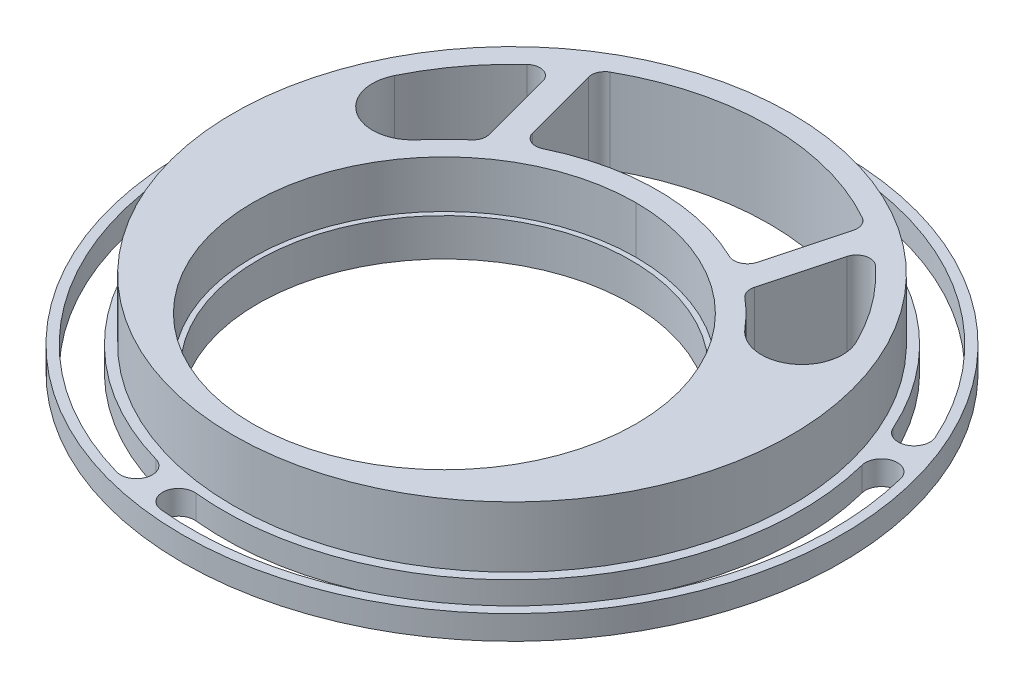
SolidWorks part; units mm, degrees
material "7075-T6, Plate (SS)"
ref_plane "X-Y Datum" through (0, 0, 0) normal (0, 0, 1) x (1, 0, 0)
ref_plane "X-Z Datum" through (0, 0, 0) normal (0, 1, 0) x (1, 0, 0)
ref_plane "Y-Z Datum" through (0, 0, 0) normal (1, 0, 0) x (0, 0, -1)
sketch "Sketch1" plane through (0, 0, 0) normal (0, 1, 0) x (1, 0, 0)
  line L0 (0, 0) -> (0, -12.7) construction
  line L1 (0, -43.0151) -> (0, 43.0151) construction
  line L2 (0, 61.9125) -> (0, 52.3875)
  circle A0 centre (0, -12.7) radius 35.052
  circle A1 centre (0, 0) radius 52.3875 construction
  circle A2 centre (0, 0) radius 57.15 construction
  circle A3 centre (0, 0) radius 61.9125
  point P12 (0, 57.15)
  dimension "D2" = 70.104
  dimension "D3" = 104.775
  dimension "D4" = 123.825
  dimension "D5" = 114.3
  dimension "D1" = 12.7
extrude "Boss-Extrude1" add sketch "Sketch1" along normal blind 4.5212 contours A3 A0 region at (-42.5405, 0, 42.5405)
sketch "Sketch3" plane through (0, 4.5212, 0) normal (0, 1, 0) x (1, 0, 0)
  circle A0 centre (0, 0) radius 52.3875 construction
  circle A1 centre (0, 0) radius 52.3875
extrude "Boss-Extrude2" add sketch "Sketch3" along normal blind 11.43
sketch "Sketch4" plane through (0, 0, 0) normal (0, -1, 0) x (1, 0, 0)
  circle A0 centre (0, 12.7) radius 35.052 construction
  circle A1 centre (0, 12.7) radius 35.052
extrude "Cut-Extrude1" cut sketch "Sketch4" against normal through all
sketch "Sketch9" plane through (0, 15.9512, 0) normal (0, 1, 0) x (1, 0, 0)
  circle A0 centre (0, -12.7) radius 35.052 construction
  circle A1 centre (0, -12.7) radius 35.052 construction
  circle A2 centre (0, -12.7) radius 36
  dimension "D1" = 72
extrude "Cut-Extrude3" cut sketch "Sketch9" against normal blind 8.89
ref_point "Point1"
ref_plane "Plane1" through (0, 0, 0) normal (1, 0, 0) x (0, 0, -1)
split line "Split Line1"
ref_plane "Plane2" through (0, 7.9756, 0) normal (0, 1, 0) x (1, 0, 0)
sketch "Sketch14" plane through (0, 7.9756, 0) normal (0, 1, 0) x (1, 0, 0)
  circle A0 centre (-33.2491, 22.3603) radius 8.255
ref_point "Point4"
sketch "Sketch10" plane through (0, 15.9512, 0) normal (0, 1, 0) x (1, 0, 0)
  line L0 (-34.8427, 33.4836) -> (-25.0086, 18.6)
  line L1 (-28.7442, 38.845) -> (-18.6301, 22.7689)
  line L2 (0, -12.7) -> (0, 61.9125) construction
  line L3 (29.4814, 39.9164) -> (18.7157, 24.2692)
  line L4 (35.2451, 34.9321) -> (25.2336, 20.1674)
  circle A0 centre (0, 0) radius 52.3875 construction
  circle A1 centre (0, 0) radius 52.3875 construction
  arc A7 (0, -52.764) -> (0, 27.364) centre (0, -12.7) ccw
  arc A8 (0, 27.364) -> (0, -52.764) centre (0, -12.7) ccw
  arc A9 (0, -52.764) -> (0, 27.364) centre (0, -12.7) ccw construction
  arc A10 (0, 27.364) -> (0, -52.764) centre (0, -12.7) ccw construction
  circle A29 centre (0, 0) radius 48.3235 construction
  arc A30 (-30.6977, 13.0444) -> (30.6977, 13.0444) centre (0, -12.7) cw
  arc A31 (-43.3761, 21.2996) -> (43.3761, 21.2996) centre (0, 0) cw
  arc A34 (-30.6977, 13.0444) -> (-43.3761, 21.2996) centre (-36.5363, 17.9409) cw
  arc A35 (43.3761, 21.2996) -> (30.6977, 13.0444) centre (36.5363, 17.9409) cw
  arc A36 (-34.8427, 33.4836) -> (-28.7442, 38.845) centre (0, 0) cw
  arc A37 (35.2451, 34.9321) -> (29.4814, 39.9164) centre (0, 0) ccw
  arc A38 (-25.0086, 18.6) -> (-18.6301, 22.7689) centre (0, -12.7) cw
  arc A39 (18.7157, 24.2692) -> (25.2336, 20.1674) centre (0, -12.7) cw
  arc A40 (-32.6439, 14.6766) -> (-5.9167, 29.4912) centre (0, -12.7) cw construction
  arc A41 (32.6439, 14.6766) -> (5.8124, 29.5056) centre (0, -12.7) ccw construction
  arc A42 (-28.7442, 38.845) -> (28.7442, 38.845) centre (0, 0) cw
  point P35 (0, 48.3235)
  dimension "D3" = 7.62
  dimension "D5" = 7.62
  dimension "D6" = 7.7012
  dimension "D7" = 7.62
  dimension "D1" = 4.064
  dimension "D2" = 4.064
extrude "Cut-Extrude5" cut sketch "Sketch10" against normal through all contours A35 A31 A34 A30
sketch "Sketch15" plane through (0, 7.9756, 0) normal (0, 1, 0) x (1, 0, 0)
  line L1 (-2.1171, 31.2835) -> (-2.1171, 43.3958)
  line L4 (2.032, 31.291) -> (2.032, 43.4389)
  line L6 (-2.1764, 48.3235) -> (-2.1667, 48.2749) construction
  line L8 (2.1667, 48.2749) -> (2.1764, 48.3235) construction
  arc A0 (30.6977, 13.0444) -> (-30.6977, 13.0444) centre (0, -12.7) ccw construction
  arc A1 (30.6977, 13.0444) -> (-30.6977, 13.0444) centre (0, -12.7) ccw construction
  arc A2 (43.3761, 21.2996) -> (-43.3761, 21.2996) centre (0, 0) ccw construction
  arc A3 (-2.1171, 43.3958) -> (-6.9062, 47.8275) centre (-6.5621, 43.3958) ccw
  arc A4 (43.3761, 21.2996) -> (-43.3761, 21.2996) centre (0, 0) ccw construction
  arc A5 (6.5037, 47.8838) -> (2.032, 43.4389) centre (6.477, 43.4389) ccw
  arc A7 (-2.1171, 31.2835) -> (-5.362, 27.0036) centre (-6.5621, 31.2835) cw
  arc A9 (2.032, 31.291) -> (5.2509, 27.0184) centre (6.477, 31.291) ccw
  arc A10 (-6.9062, 47.8275) -> (6.5037, 47.8838) centre (0, 0) cw
  arc A11 (-5.362, 27.0036) -> (5.2509, 27.0184) centre (0, -12.7) cw
  point P9 (0, 37.4715)
  dimension "D1" = 4.445
  dimension "D2" = 2.1171
  dimension "D3" = 4.445
  dimension "D4" = 2.032
  dimension "D5" = 43.4389
  dimension "D6" = 31.2835
  dimension "D7" = 2.1171
  dimension "D8" = 12.148
  dimension "D9" = 12.1123
extrude "Boss-Extrude3" [suppressed] add sketch "Sketch15" along normal up to surface and the other way up to surface contours A9 L4 A5 A10 A3 L1 A7 A11 up to face at (0, 15.9512, 52.3875) other way up to face at (0, 0, 47.752)
sketch "Sketch20" plane through (0, 4.5212, 0) normal (0, 1, 0) x (1, 0, 0)
  circle A0 centre (0, 0) radius 52.3875
  circle A2 centre (0, 0) radius 66.6087
sketch "Sketch25" [suppressed] plane through (0, 15.9512, 0) normal (0, 1, 0) x (1, 0, 0)
  line L6 (-4.6571, 31.2835) -> (-4.6571, 43.3958)
  line L7 (-4.6571, 31.2835) -> (-4.6571, 43.3958)
  line L12 (4.572, 43.4389) -> (4.572, 31.291)
  line L13 (4.572, 43.4389) -> (4.572, 31.291)
  circle A1 centre (-51.685, -7.6867) radius 0.134
  circle A2 centre (49.3335, -18.9489) radius 0.46
  arc A3 (48.8818, -18.8622) -> (48.9404, -18.71) centre (-0.2183, 0.1504) ccw
  arc A4 (48.8818, -18.8622) -> (48.9404, -18.71) centre (-0.2183, 0.1504) ccw
  arc A45 (-4.6571, 43.3958) -> (-6.6423, 45.2991) centre (-6.5621, 43.3958) ccw
  arc A46 (-5.9167, 29.4912) -> (-4.6571, 31.2835) centre (-6.5621, 31.2835) ccw
  arc A47 (-5.9167, 29.4912) -> (-32.6439, 14.6766) centre (0, -12.7) ccw
  arc A48 (-41.0962, 20.18) -> (-32.6439, 14.6766) centre (-36.5363, 17.9409) ccw
  arc A49 (-6.6423, 45.2991) -> (-41.0962, 20.18) centre (0, 0) ccw
  arc A50 (-4.6571, 43.3958) -> (-6.6423, 45.2991) centre (-6.5621, 43.3958) ccw
  arc A51 (-5.9167, 29.4912) -> (-4.6571, 31.2835) centre (-6.5621, 31.2835) ccw
  arc A52 (-5.9167, 29.4912) -> (-32.6439, 14.6766) centre (0, -12.7) ccw
  arc A53 (-41.0962, 20.18) -> (-32.6439, 14.6766) centre (-36.5363, 17.9409) ccw
  arc A54 (-6.6423, 45.2991) -> (-41.0962, 20.18) centre (0, 0) ccw
  circle A68 centre (-0.2183, 0.1504) radius 52.1224
  circle A69 centre (0, -12.7) radius 32.512
  circle A70 centre (0, -12.7) radius 32.512
  arc A72 (32.6439, 14.6766) -> (41.0962, 20.18) centre (36.5363, 17.9409) ccw
  arc A73 (4.572, 31.291) -> (5.8124, 29.5056) centre (6.477, 31.291) ccw
  arc A74 (32.6439, 14.6766) -> (5.8124, 29.5056) centre (0, -12.7) ccw
  arc A75 (41.0962, 20.18) -> (6.3564, 45.3401) centre (0, 0) ccw
  arc A76 (6.3564, 45.3401) -> (4.572, 43.4389) centre (6.477, 43.4389) ccw
  arc A77 (32.6439, 14.6766) -> (41.0962, 20.18) centre (36.5363, 17.9409) ccw
  arc A78 (4.572, 31.291) -> (5.8124, 29.5056) centre (6.477, 31.291) ccw
  arc A79 (32.6439, 14.6766) -> (5.8124, 29.5056) centre (0, -12.7) ccw
  arc A80 (41.0962, 20.18) -> (6.3564, 45.3401) centre (0, 0) ccw
  arc A81 (6.3564, 45.3401) -> (4.572, 43.4389) centre (6.477, 43.4389) ccw
  dimension "D1" = 2.54
  dimension "D2" = 2.54
  dimension "D3" = 2.54
ref_axis "Axis1" [suppressed] through (0, 0, 0) along (0, 0, -1)
sketch "Sketch26" plane through (0, 4.5212, 0) normal (0, 1, 0) x (1, 0, 0)
  line L0 (0, 0) -> (-44.5876, 35.8758)
  line L1 (0, 0) -> (-12.699, -55.802)
  arc A0 (-46.3431, 33.443) -> (-15.5853, -54.9838) centre (0, 0) ccw construction
  arc A1 (-48.7758, 35.1986) -> (-16.4034, -57.8701) centre (0, 0) ccw
  arc A2 (-43.9104, 31.6875) -> (-14.7672, -52.0975) centre (0, 0) ccw
  arc A3 (-43.9104, 31.6875) -> (-48.7758, 35.1986) centre (-46.3431, 33.443) ccw
  arc A4 (-16.4034, -57.8701) -> (-14.7672, -52.0975) centre (-15.5853, -54.9838) ccw
  point P4 (-53.9779, -18.7753)
  dimension "D2" = 3
  dimension "D1" = 57.15
  dimension "D3" = 116
extrude "Cut-Extrude6" cut sketch "Sketch26" against normal up to surface (4.5212 mm away) contours A2 A4 A1 A3 up to face at (0, 0, 47.752)
pattern_circular "CirPattern2" count 3 over 360 about axis through (0, 4.5212, 0) along (0, 1, 0) of "Cut-Extrude6"
sketch "Sketch31" [suppressed] plane through (0, 17.2212, 0) normal (0, 1, 0) x (1, 0, 0)
  line L4 (-32.7966, 31.9455) -> (-25.0611, 21.7535)
  line L5 (-27.0439, 36.9426) -> (-18.5227, 25.6668)
  line L6 (0, -12.7) -> (0, 61.9125) construction
  line L8 (27.0439, 36.9426) -> (18.5284, 25.6625)
  line L9 (32.7966, 31.9455) -> (25.132, 21.7001)
  arc A0 (-32.7966, 31.9455) -> (-27.0439, 36.9426) centre (0, 0) cw
  arc A1 (32.7966, 31.9455) -> (27.0439, 36.9426) centre (0, 0) ccw
  arc A2 (-25.0611, 21.7535) -> (-18.5227, 25.6668) centre (0, -12.7) cw
  arc A3 (18.5284, 25.6625) -> (25.132, 21.7001) centre (0, -12.7) cw
  arc A12 (-5.9167, 29.4912) -> (-32.6439, 14.6766) centre (0, -12.7) ccw construction
  arc A13 (-32.6439, 14.6766) -> (-5.9167, 29.4912) centre (0, -12.7) cw construction
  arc A14 (32.6439, 14.6766) -> (5.8124, 29.5056) centre (0, -12.7) ccw construction
  arc A15 (4.572, 31.291) -> (5.8124, 29.5056) centre (6.477, 31.291) ccw construction
  arc A16 (41.0962, 20.18) -> (6.3564, 45.3401) centre (0, 0) ccw construction
  arc A17 (-27.0439, 36.9426) -> (27.0439, 36.9426) centre (0, 0) cw
  circle A18 centre (0, 0) radius 61.9125 construction
  arc A20 (-6.6423, 45.2991) -> (-41.0962, 20.18) centre (0, 0) ccw construction
  point P18 (0, 45.7835)
  dimension "D1" = 7.62
  dimension "D2" = 7.62
  dimension "D3" = 7.62
  dimension "D4" = 7.7012
sketch "Sketch33" [suppressed] plane through (0, 0, 0) normal (0, -1, 0) x (1, 0, 0)
  line L0 (29.5753, -38.216) -> (20.1732, -21.9145)
  line L1 (25.4, -41.1096) -> (15.6309, -24.189)
  line L2 (-25.4, -41.1096) -> (-15.6309, -24.189)
  line L3 (-29.5753, -38.216) -> (-20.1732, -21.9145)
  line L4 (2.032, -43.4389) -> (2.032, -31.291) construction
  line L5 (-2.1171, -43.3958) -> (-2.1171, -31.2835) construction
  line L6 (25.4, -41.1096) -> (-25.4, -41.1096) construction
  line L7 (0, 12.7) -> (0, -61.9125) construction
  arc A0 (29.5753, -38.216) -> (25.4, -41.1096) centre (0, 0) cw
  arc A1 (6.5037, -47.8838) -> (43.3761, -21.2996) centre (0, 0) ccw construction
  arc A2 (-25.4, -41.1096) -> (-29.5753, -38.216) centre (0, 0) cw
  arc A3 (-43.3761, -21.2996) -> (-6.9062, -47.8275) centre (0, 0) ccw construction
  arc A4 (20.1732, -21.9145) -> (15.6309, -24.189) centre (0, 12.7) cw
  arc A5 (5.2509, -27.0184) -> (30.6977, -13.0444) centre (0, 12.7) ccw construction
  arc A7 (-25.4, -41.1096) -> (25.4, -41.1096) centre (0, 0) ccw construction
  circle A8 centre (0, 0) radius 61.9125 construction
  arc A9 (-15.6309, -24.189) -> (-20.1732, -21.9145) centre (0, 12.7) cw
  arc A10 (-30.6977, -13.0444) -> (-5.362, -27.0036) centre (0, 12.7) ccw construction
  point P33 (0, -41.1096)
  dimension "D3" = 50.8
  dimension "D1" = 30
  dimension "D2" = 30
  dimension "D4" = 5.08
  dimension "D5" = 5.08
  dimension "D6" = 5.08
  dimension "D7" = 5.08
sketch "Sketch34" [suppressed] plane through (0, 17.2212, 0) normal (0, 1, 0) x (1, 0, 0)
  line L0 (-15.7141, 43.0023) -> (-9.2467, 28.8885)
  line L1 (13.1348, 43.8589) -> (10.1645, 28.6737)
  arc A0 (-15.7141, 43.0023) -> (13.1348, 43.8589) centre (0, 0) cw
  arc A1 (-6.6423, 45.2991) -> (-24.1294, 38.9089) centre (0, 0) ccw construction
  arc A2 (-9.2467, 28.8885) -> (10.1645, 28.6737) centre (0, -12.7) cw
  arc A3 (-5.9167, 29.4912) -> (-16.9099, 26.4044) centre (0, -12.7) ccw construction
extrude "Cut-Extrude7" [suppressed] cut sketch "Sketch34" against normal through all
sketch "Sketch35" [suppressed] plane through (0, 0, 0) normal (0, -1, 0) x (1, 0, 0)
  line L0 (-6.9953, -26.7486) -> (-11.7037, -46.8848)
  line L1 (8.2748, -26.3808) -> (11.7753, -46.8669)
  arc A0 (-11.7037, -46.8848) -> (11.7753, -46.8669) centre (0, 0) ccw
  arc A1 (-25.4, -41.1096) -> (-6.9062, -47.8275) centre (0, 0) ccw construction
  arc A2 (-6.9953, -26.7486) -> (8.2748, -26.3808) centre (0, 0) ccw
  arc A3 (-15.6309, -24.189) -> (-5.362, -27.0036) centre (0, 12.7) ccw construction
fillet "Fillet3" [suppressed] radius 2.54
sketch "Sketch36" plane through (0, 0, 0) normal (0, -1, 0) x (1, 0, 0)
  line L0 (29.5753, -38.216) -> (24.4575, -19.0325)
  line L1 (25.4, -41.1096) -> (20.2454, -21.8724)
  line L2 (-25.4, -41.1096) -> (-20.2454, -21.8724)
  line L3 (-29.5753, -38.216) -> (-24.4575, -19.0325)
  line L4 (25.4, -41.1096) -> (-25.4, -41.1096) construction
  line L5 (0, 0) -> (0, -61.9125) construction
  arc A0 (29.5753, -38.216) -> (25.4, -41.1096) centre (0, 0) cw
  arc A1 (-25.4, -41.1096) -> (-29.5753, -38.216) centre (0, 0) cw
  arc A2 (24.4575, -19.0325) -> (20.2454, -21.8724) centre (0, 12.7) cw
  arc A3 (-25.4, -41.1096) -> (25.4, -41.1096) centre (0, 0) ccw construction
  arc A4 (-20.2454, -21.8724) -> (-24.4575, -19.0325) centre (0, 12.7) cw
  arc A5 (-43.3761, -21.2996) -> (43.3761, -21.2996) centre (0, 0) ccw construction
  arc A6 (-30.6977, -13.0444) -> (30.6977, -13.0444) centre (0, 12.7) ccw construction
  arc A7 (-30.6977, -13.0444) -> (30.6977, -13.0444) centre (0, 12.7) ccw construction
  circle A8 centre (0, 0) radius 61.9125 construction
  point P10 (0, -41.1096)
  dimension "D1" = 50.8
  dimension "D2" = 5.08
  dimension "D3" = 5.08
  dimension "D4" = 5.08
  dimension "D5" = 5.08
  dimension "D6" = 15
  dimension "D7" = 15
extrude "Boss-Extrude4" add sketch "Sketch36" against normal up to surface (15.9512 mm away) up to face at (0, 15.9512, 52.3875)
fillet "Fillet5" radius 2.54 8 edges at (29.5753, 7.9756, -38.216) (24.4575, 7.9756, -19.0325) (20.2454, 7.9756, -21.8724) (25.4, 7.9756, -41.1096) (-24.4575, 7.9756, -19.0325) (-29.5753, 7.9756, -38.216) (-20.2454, 7.9756, -21.8724) (-25.4, 7.9756, -41.1096)
equation "\"NumSlots\"= 3"
equation "\"SlotAngSpacing\"= 4deg"
equation "\"SlotAngDim\"= 360deg / \"NumSlots\""
equation "\"SlotDim\"= \"SlotAngDim\" - \"SlotAngSpacing\""
equation "\"CutoutEndRad\"= .3in"
equation "\"Slot_Length\"= 4 in"
